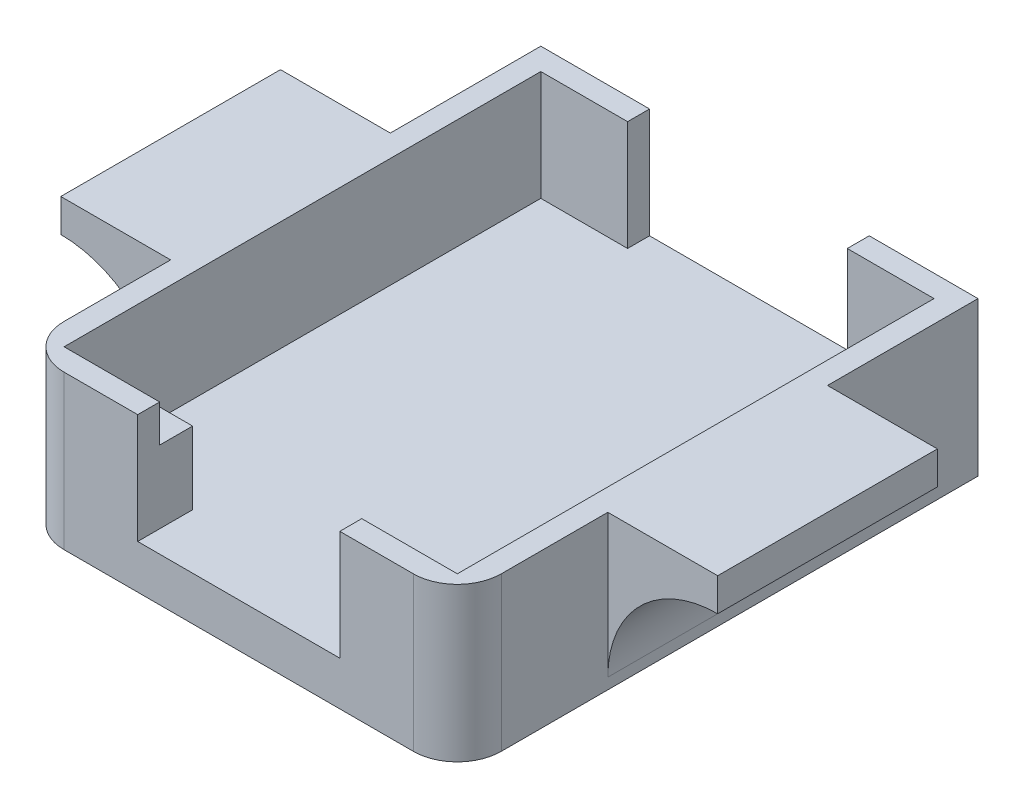
SolidWorks part; units mm, degrees
ref_plane "Front Plane" through (0, 0, 0) normal (0, 0, 1) x (1, 0, 0)
ref_plane "Top Plane" through (0, 0, 0) normal (0, 1, 0) x (1, 0, 0)
ref_plane "Right Plane" through (0, 0, 0) normal (1, 0, 0) x (0, 0, -1)
sketch "Sketch1" plane through (0, 0, 0) normal (0, 1, 0) x (1, 0, 0)
  line L1 (-8.95, 10.85) -> (8.95, 10.85)
  line L2 (-8.95, 10.85) -> (-8.95, -10.85)
  line L3 (-8.95, -10.85) -> (8.95, -10.85)
  line L4 (8.95, 10.85) -> (8.95, -10.85)
  line L5 (0, -44.7868) -> (0, 44.7868) construction
  line L6 (-44.2539, 0) -> (44.2539, 0) construction
  dimension "D1" = 21.7
  dimension "D2" = 17.9
  dimension "D3" = 8.95
  dimension "D4" = 10.85
extrude "Boss-Extrude1" add sketch "Sketch1" along normal blind 2
sketch "Sketch2" plane through (0, 0, 0) normal (0, 1, 0) x (1, 0, 0)
  line L0 (0, -44.7868) -> (0, 44.7868) construction
  line L1 (-9.95, 11.85) -> (9.95, 11.85)
  line L2 (-9.95, 11.85) -> (-9.95, -11.85)
  line L3 (-9.95, -11.85) -> (9.95, -11.85)
  line L4 (9.95, 11.85) -> (9.95, -11.85)
  line L5 (-44.2539, 0) -> (44.2539, 0) construction
  line L21 (-8.95, 10.85) -> (8.95, 10.85)
  line L22 (-8.95, 10.85) -> (-8.95, -10.85)
  line L23 (-8.95, -10.85) -> (8.95, -10.85)
  line L24 (8.95, 10.85) -> (8.95, -10.85)
  line L25 (-8.95, -10.85) -> (-4.6, -10.85)
  line L26 (-8.95, -10.85) -> (-8.95, -9.35)
  line L27 (-8.95, -9.35) -> (-4.6, -9.35)
  line L28 (-4.6, -10.85) -> (-4.6, -9.35)
  line L29 (4.6, -10.85) -> (8.95, -10.85)
  line L30 (4.6, -10.85) -> (4.6, -9.35)
  line L31 (4.6, -9.35) -> (8.95, -9.35)
  line L32 (8.95, -10.85) -> (8.95, -9.35)
  dimension "D1" = 23.7
  dimension "D2" = 19.9
  dimension "D3" = 9.95
  dimension "D4" = 11.85
  dimension "D5" = 9.2
  dimension "D6" = 1.5
extrude "Boss-Extrude2" add sketch "Sketch2" along normal blind 7 contours L4 L1 L2 L3 | L26 L27 L28 L25 | L31 L32 L29 L30 region at (0, 0, -11.5405)
sketch "Sketch3" plane through (0, 0, -10.85) normal (0, 0, 1) x (1, 0, 0)
  line L0 (-9.95, 7) -> (9.95, 7) construction
  line L1 (-5, 7) -> (5, 7)
  line L2 (-5, 7) -> (-5, 2)
  line L3 (-5, 2) -> (5, 2)
  line L4 (5, 7) -> (5, 2)
  line L5 (0, -44.7868) -> (0, 44.7868) construction
  dimension "D1" = 5
  dimension "D2" = 10
  dimension "D3" = 5
extrude "Cut-Extrude1" cut sketch "Sketch3" against normal up to surface (1 mm away) up to face at (0, 3.5, -11.85)
sketch "Sketch4" plane through (0, 0, 11.85) normal (0, 0, 1) x (1, 0, 0)
  line L0 (-9.95, 7) -> (9.95, 7) construction
  line L1 (-4.6, 7) -> (4.6, 7)
  line L2 (-4.6, 7) -> (-4.6, 2)
  line L3 (-4.6, 2) -> (4.6, 2)
  line L4 (4.6, 7) -> (4.6, 2)
  line L5 (0, -44.7868) -> (0, 44.7868) construction
  dimension "D1" = 9.2
  dimension "D2" = 4.6
  dimension "D3" = 5
extrude "Cut-Extrude2" cut sketch "Sketch4" against normal up to surface (1 mm away) up to face at (0, 4.5, 10.85)
sketch "Sketch7" plane through (0, 7, 0) normal (0, 1, 0) x (1, 0, 0)
  line L0 (-9.95, 11.85) -> (-9.95, -11.85) construction
  line L1 (-9.95, 5) -> (-14.95, 5)
  line L2 (-9.95, 5) -> (-9.95, -5)
  line L3 (-9.95, -5) -> (-14.95, -5)
  line L4 (-14.95, 5) -> (-14.95, -5)
  line L5 (9.95, 11.85) -> (9.95, -11.85) construction
  line L6 (9.95, 5) -> (14.95, 5)
  line L7 (9.95, 5) -> (9.95, -5)
  line L8 (9.95, -5) -> (14.95, -5)
  line L9 (14.95, 5) -> (14.95, -5)
  line L10 (-44.2539, 0) -> (44.2539, 0) construction
  point P12 (0, 0)
  dimension "D1" = 10
  dimension "D2" = 5
  dimension "D3" = 5
extrude "Boss-Extrude3" add sketch "Sketch7" against normal blind 1.5
fillet "Fillet1" radius 5 2 edges at (9.95, 5.5, 0) (-9.95, 5.5, 0)
sketch "Sketch8" plane through (0, 7, 0) normal (0, 1, 0) x (1, 0, 0)
  line L0 (-8.95, 10.85) -> (-8.95, -9.35) construction
  line L1 (-4.6, -9.35) -> (-8.95, -9.35)
  line L2 (-4.6, -9.35) -> (-4.6, -10.85)
  line L3 (-4.6, -10.85) -> (-8.95, -10.85)
  line L4 (-8.95, -9.35) -> (-8.95, -10.85)
  line L5 (4.6, -9.35) -> (8.95, -9.35)
  line L6 (4.6, -9.35) -> (4.6, -10.85)
  line L7 (4.6, -10.85) -> (8.95, -10.85)
  line L8 (8.95, -9.35) -> (8.95, -10.85)
  point P9 (0, 0)
  dimension "D1" = 1.5
extrude "Cut-Extrude4" cut sketch "Sketch8" against normal blind 1.7
fillet "Fillet3" radius 2 2 edges at (9.95, 3.5, 11.85) (-9.95, 3.5, 11.85)
equation "\"len\"=21.7"
equation "\"D1@Sketch1\"=\"len\""
equation "\"wid\"=17.9"
equation "\"D2@Sketch1\"=\"wid\""
equation "\"D3@Sketch1\"=\"wid\"/2"
equation "\"D4@Sketch1\"=\"len\"/2"
equation "\"D1@Sketch2\"=\"len\"+2"
equation "\"D2@Sketch2\"=\"wid\"+2"
equation "\"D3@Sketch2\"=(\"wid\"+2)/2"
equation "\"D4@Sketch2\"=(\"len\" +2)/2"
